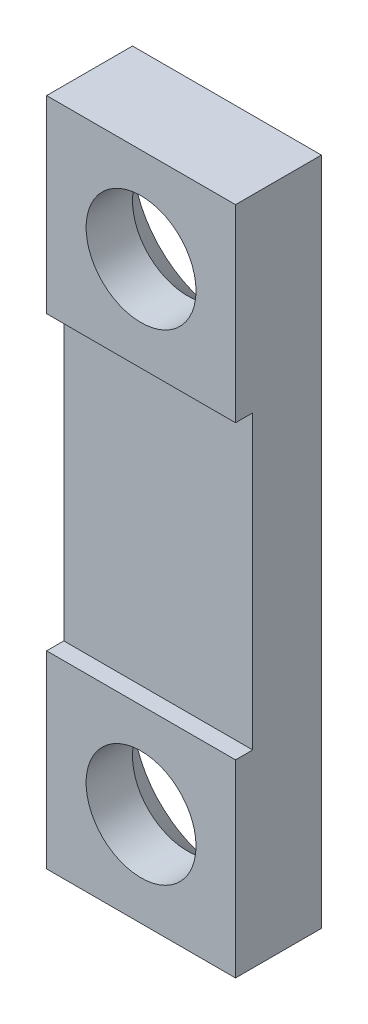
SolidWorks part; units mm, degrees
ref_plane "Front Plane" through (0, 0, 0) normal (1, 0, 0) x (0, 1, 0)
ref_plane "Top Plane" through (0, 0, 0) normal (0, 0, 1) x (0, 1, 0)
ref_plane "Right Plane" through (0, 0, 0) normal (0, 1, 0) x (-1, 0, 0)
sketch "Sketch1" plane through (0, 0, 0) normal (0, 0, 1) x (0, 1, 0)
  line L0 (-7, 0) -> (7, 0) construction
  line L1 (-9.75, 2.75) -> (9.75, 2.75)
  line L2 (-9.75, 2.75) -> (-9.75, -2.75)
  line L3 (-9.75, -2.75) -> (9.75, -2.75)
  line L4 (9.75, 2.75) -> (9.75, -2.75)
  line L5 (4.25, 2.75) -> (4.25, -2.75)
  line L6 (-4.25, 2.75) -> (-4.25, -2.75)
  circle A0 centre (7, 0) radius 1.6
  circle A1 centre (-7, 0) radius 1.6
  point P6 (0, 0)
  dimension "D6" = 3.2
  dimension "D7" = 3.2
  dimension "D8" = 2.75
  dimension "D1" = 19.5
  dimension "D2" = 5.5
  dimension "D3" = 14
  dimension "D4" = 2.75
  dimension "D5" = 2.75
  dimension "D9" = 2.75
extrude "Boss-Extrude1" add sketch "Sketch1" along normal blind 2.5 contours A1 L6 L1 L2 L3 | L1 L5 A0 L3 L4 region at (-2.6722, -7, 0) region at (-2.6722, 7, 0)
extrude "Boss-Extrude2" add sketch "Sketch1<4>" along normal blind 2 contours L0 L6 L3 L5 | L6 L0 L5 L1 region at (-1.375, 0, 0) region at (1.375, 0, 0)
sketch "Sketch1<4>" plane through (0, 0, 0) normal (0, 0, 1) x (0, 1, 0) same geometry as "Sketch1"
chamfer "Chamfer1" distance 1.15 angle 45 2 edges at (1.6, 7, 0) (1.6, -7, 0)
